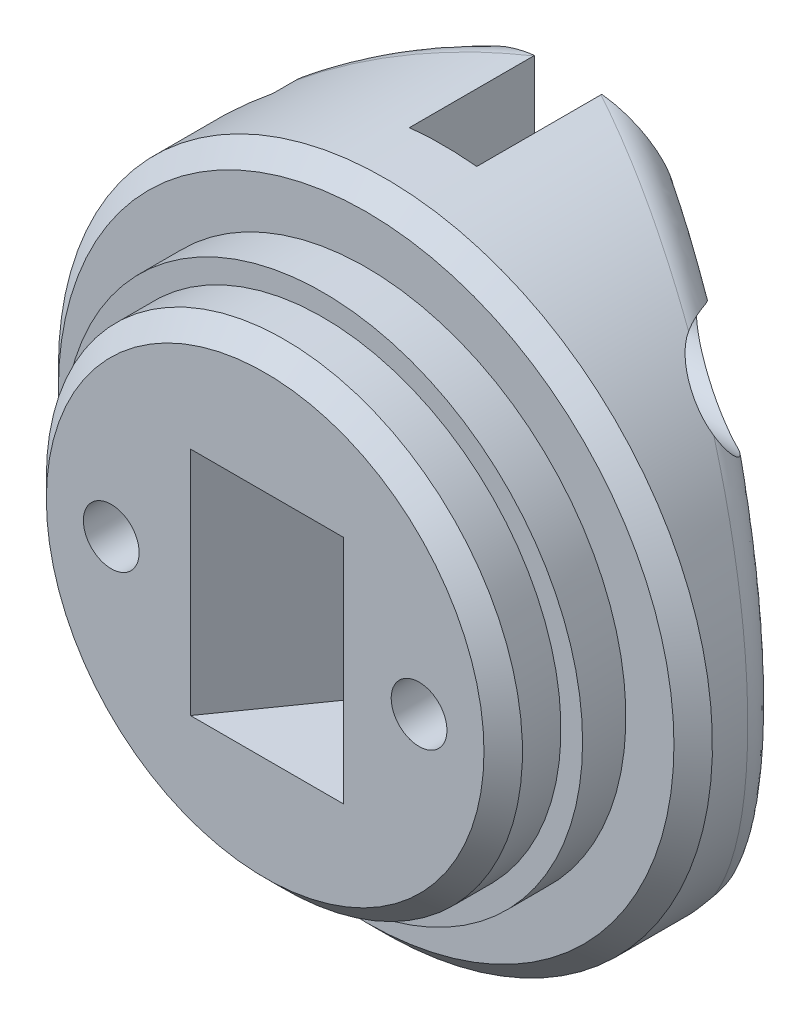
SolidWorks part; units mm, degrees
ref_plane "Front Plane" through (0, 0, 0) normal (0, 0, 1) x (1, 0, 0)
ref_plane "Top Plane" through (0, 0, 0) normal (0, 1, 0) x (1, 0, 0)
ref_plane "Right Plane" through (0, 0, 0) normal (1, 0, 0) x (0, 0, -1)
sketch "Sketch1" plane through (0, 0, 0) normal (0, 0, 1) x (1, 0, 0)
  circle A0 centre (0, 0) radius 12.375
  dimension "D1" = 24.75
extrude "Boss-Extrude1" add sketch "Sketch1" along normal blind 5.25
sketch "Sketch2" plane through (0, 0, 0) normal (0, 0, -1) x (-1, 0, 0)
  circle A0 centre (0, 0) radius 17
  dimension "D1" = 34
extrude "Boss-Extrude2" add sketch "Sketch2" along normal blind 4
chamfer "Chamfer1" distance 1 angle 45 1 edges at (12.375, 0, 5.25)
sketch "Sketch3" plane through (0, 0, 0) normal (0, 1, 0) x (1, 0, 0)
  line L0 (0, 0) -> (0, 10.5) construction
  line L1 (-17, 4) -> (-5.524, 10.5)
  line L2 (-5.524, 10.5) -> (-1.75, 10.5)
  line L3 (-1.75, 10.5) -> (-1.75, 4)
  line L4 (17, 4) -> (-17, 4) construction
  line L5 (-17, 4) -> (-1.75, 4)
  line L6 (17, 4) -> (1.75, 4)
  line L7 (1.75, 10.5) -> (1.75, 4)
  line L8 (5.524, 10.5) -> (1.75, 10.5)
  line L9 (17, 4) -> (5.524, 10.5)
  dimension "D1" = 3.5
  dimension "D2" = 6.5
extrude "Boss-Extrude3" add sketch "Sketch3" along normal mid plane 40
sketch "Sketch4" plane through (0, 0, 0) normal (1, 0, 0) x (0, 0, -1)
  line L0 (6.75, 11) -> (6.75, -11) construction
  line L1 (10.5, 20) -> (10.5, -20) construction
  circle A0 centre (6.75, 11) radius 1.25
  circle A1 centre (6.75, -11) radius 1.25
  point P4 (6.75, 0)
  dimension "D1" = 2.5
  dimension "D2" = 22
  dimension "D3" = 3.75
extrude "Cut-Extrude1" cut sketch "Sketch4" against normal through all both and the other way through all
sketch "Sketch5" plane through (0, 0, 0) normal (0, 0, 1) x (1, 0, 0)
  circle A0 centre (0, 0) radius 13.5
  dimension "D1" = 27
extrude "Boss-Extrude4" add sketch "Sketch5" along normal blind 2.25
sketch "Sketch6" plane through (0, 0, 5.25) normal (0, 0, 1) x (1, 0, 0)
  line L1 (23.3622, -22.945) -> (-23.3622, -22.945)
  line L2 (23.3622, -22.945) -> (23.3622, 22.945)
  line L3 (23.3622, 22.945) -> (-23.3622, 22.945)
  line L4 (-23.3622, -22.945) -> (-23.3622, 22.945)
  line L5 (23.3622, -22.945) -> (-23.3622, 22.945) construction
  line L6 (23.3622, 22.945) -> (-23.3622, -22.945) construction
  circle A0 centre (0, 0) radius 17
  arc A1 (1.75, -16.9097) -> (17, 0) centre (0, 0) ccw construction
extrude "Cut-Extrude2" cut sketch "Sketch6" against normal through all both and the other way through all
sketch "Sketch7" plane through (0, 0, -4) normal (0, 0, -1) x (-1, 0, 0)
  line L0 (1.75, 16.9097) -> (1.75, -16.9097) construction
  line L1 (-1.75, 7) -> (1.75, 7)
  line L2 (-1.75, 7) -> (-1.75, -7)
  line L3 (-1.75, -7) -> (1.75, -7)
  line L4 (1.75, 7) -> (1.75, -7)
  line L5 (-1.75, 7) -> (1.75, -7) construction
  line L6 (-1.75, -7) -> (1.75, 7) construction
  point P0 (0, 0)
  dimension "D1" = 14
extrude "Cut-Extrude3" cut sketch "Sketch7" against normal blind 4
sketch "Sketch8" plane through (0, 0, 0) normal (1, 0, 0) x (0, 0, -1)
  circle A0 centre (6.75, 11) radius 2.25
  circle A1 centre (6.75, -11) radius 2.25
  dimension "D1" = 4.5
extrude "Cut-Extrude4" cut sketch "Sketch8" along normal blind 33 from offset 6
sketch "Sketch9" plane through (0, 0, 0) normal (1, 0, 0) x (0, 0, -1)
  line L1 (8.3377, 8.25) -> (9.9254, 11)
  line L2 (9.9254, 11) -> (8.3377, 13.75)
  line L3 (8.3377, 13.75) -> (5.1623, 13.75)
  line L4 (5.1623, 13.75) -> (3.5746, 11)
  line L5 (3.5746, 11) -> (5.1623, 8.25)
  line L6 (5.1623, 8.25) -> (8.3377, 8.25)
  line L7 (5.1623, -13.75) -> (8.3377, -13.75)
  line L8 (8.3377, -13.75) -> (9.9254, -11)
  line L9 (9.9254, -11) -> (8.3377, -8.25)
  line L10 (8.3377, -8.25) -> (5.1623, -8.25)
  line L11 (5.1623, -8.25) -> (3.5746, -11)
  line L12 (3.5746, -11) -> (5.1623, -13.75)
  circle A0 centre (6.75, 11) radius 2.75 construction
  circle A1 centre (6.75, -11) radius 2.75 construction
  dimension "D1" = 5.5
extrude "Cut-Extrude5" cut sketch "Sketch9" against normal blind 33 from offset 5 offset against normal yes
fillet "Fillet1" radius 2 6 edges at (8.3004, 14.8359, -8.9274) (17, 0, -4) (8.3004, -14.8359, -8.9274) (-7.8472, -15.0805, -9.1841) (-7.8472, 15.0805, -9.1841) (-17, 0, -4)
chamfer "Chamfer2" distance 1 angle 45 1 edges at (-17, 0, 0)
sketch "Sketch10" plane through (0, 0, 0) normal (1, 0, 0) x (0, 0, -1)
  circle A0 centre (38, 0) radius 31.5
  dimension "D1" = 63
  dimension "D2" = 38
extrude "Cut-Extrude6" cut sketch "Sketch10" against normal blind 10 from offset 6 offset against normal yes
sketch "Sketch11" plane through (0, 0, 5.25) normal (0, 0, 1) x (1, 0, 0)
  line L0 (0, 6.9351) -> (0, -4.8401) construction
  circle A0 centre (-8, 0) radius 1.45
  circle A1 centre (8, 0) radius 1.45
  dimension "D1" = 2.9
  dimension "D2" = 16
extrude "Cut-Extrude7" cut sketch "Sketch11" against normal blind 10
fillet "Fillet2" radius 1.4 2 edges at (-6.55, 0, -4.75) (6.55, 0, -4.75)
sketch "Sketch12" plane through (0, 0, 0) normal (0, 1, 0) x (1, 0, 0)
  line L0 (9.858, 14.2422) -> (-5.0057, -6.8394)
  line L1 (-5.0057, -6.8394) -> (0.3067, -10.5849)
  line L2 (0.3067, -10.5849) -> (15.974, 11.6365)
  line L3 (15.974, 11.6365) -> (9.858, 14.2422)
  line L4 (0, 0) -> (19.0507, 0) construction
  dimension "D1" = 6.5
  dimension "D2" = 54.814
  dimension "D3" = 0.15
extrude "Cut-Extrude8" cut sketch "Sketch12" against normal mid plane 12
fillet "Fillet3" radius 2 2 edges at (6.7357, 0, -9.8137) (12.4192, 0, -6.5946)
fillet "Fillet5" radius 10 1 edges at (-12.5861, 0, -6.5)
